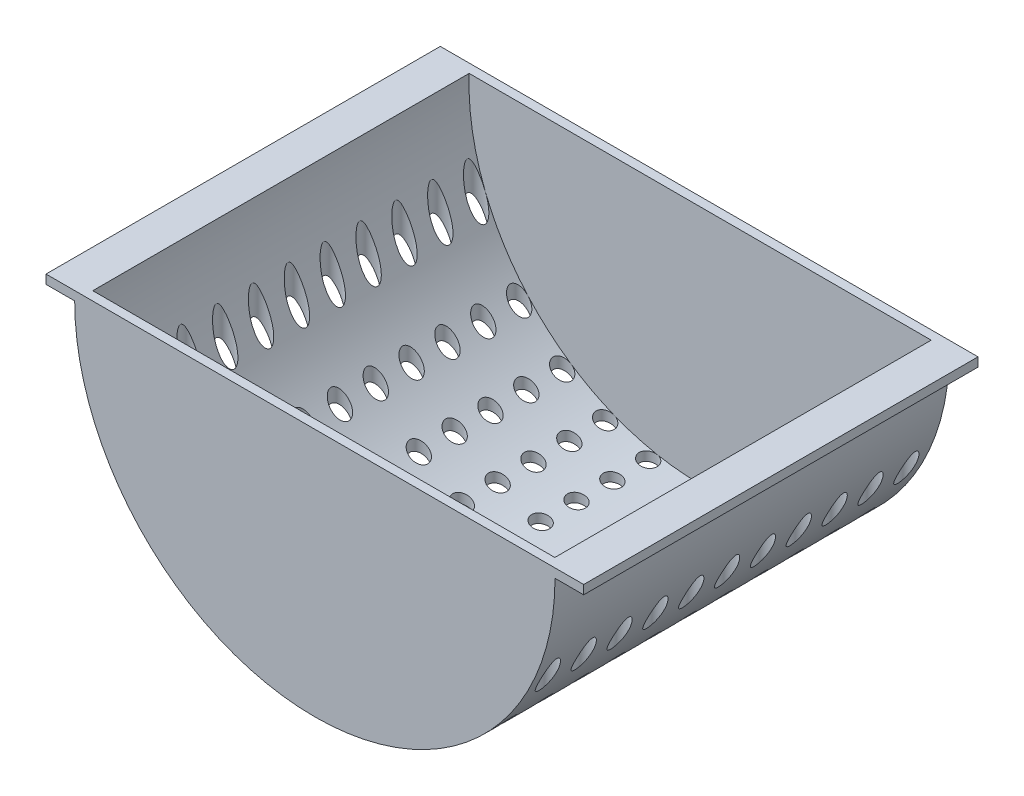
SolidWorks part; units mm, degrees
ref_plane "Plano frontal" through (0, 0, 0) normal (0, 0, 1) x (1, 0, 0)
ref_plane "Plano superior" through (0, 0, 0) normal (0, 1, 0) x (1, 0, 0)
ref_plane "Plano direito" through (0, 0, 0) normal (1, 0, 0) x (0, 0, -1)
sketch "Esboço2" plane through (0, 0, 0) normal (0, 0, 1) x (1, 0, 0)
  line L0 (0, 0) -> (-150, 0)
  line L1 (-150, 0) -> (-150, -2.5)
  line L2 (-150, -2.5) -> (-142, -2.5)
  line L3 (-8, -2.5) -> (0, -2.5)
  line L4 (0, -2.5) -> (0, 0)
  arc A0 (-142, -2.5) -> (-8, -2.5) centre (-75, -2.5) ccw
  dimension "D3" = 8
  dimension "D1" = 150
  dimension "D2" = 2.5
  dimension "D4" = 8
  dimension "D5" = 2.5
extrude "Ressalto-extrusão1" add sketch "Esboço2" along normal blind 110
shell "Casca1" thickness 2.5 removed face at (-75, 0, 55)
sketch "Esboço3" plane through (0, 0, 0) normal (0, 1, 0) x (1, 0, 0)
  line L0 (-75, -107.5) -> (-75, -2.5) construction
  line L3 (-139.4515, -55) -> (-10.5485, -55) construction
  line L4 (-139.4515, -107.5) -> (-139.4515, -2.5) construction
  line L5 (-10.5485, -107.5) -> (-10.5485, -2.5) construction
  circle A0 centre (-75, -55) radius 2.5
  circle A1 centre (-63, -55) radius 2.5
  circle A2 centre (-51, -55) radius 2.5
  circle A3 centre (-39, -55) radius 2.5
  circle A4 centre (-27, -55) radius 2.5
  circle A5 centre (-15, -55) radius 2.5
  circle A6 centre (-63, -45) radius 2.5
  circle A7 centre (-51, -45) radius 2.5
  circle A8 centre (-39, -45) radius 2.5
  circle A9 centre (-27, -45) radius 2.5
  circle A10 centre (-15, -45) radius 2.5
  circle A11 centre (-63, -35) radius 2.5
  circle A12 centre (-51, -35) radius 2.5
  circle A13 centre (-39, -35) radius 2.5
  circle A14 centre (-27, -35) radius 2.5
  circle A15 centre (-15, -35) radius 2.5
  circle A16 centre (-63, -25) radius 2.5
  circle A17 centre (-51, -25) radius 2.5
  circle A18 centre (-39, -25) radius 2.5
  circle A19 centre (-27, -25) radius 2.5
  circle A20 centre (-15, -25) radius 2.5
  circle A21 centre (-63, -15) radius 2.5
  circle A22 centre (-51, -15) radius 2.5
  circle A23 centre (-39, -15) radius 2.5
  circle A24 centre (-27, -15) radius 2.5
  circle A25 centre (-15, -15) radius 2.5
  circle A26 centre (-63, -5) radius 2.5
  circle A27 centre (-51, -5) radius 2.5
  circle A28 centre (-39, -5) radius 2.5
  circle A29 centre (-27, -5) radius 2.5
  circle A30 centre (-15, -5) radius 2.5
  circle A31 centre (-75, -45) radius 2.5
  circle A32 centre (-75, -35) radius 2.5
  circle A33 centre (-75, -25) radius 2.5
  circle A34 centre (-75, -15) radius 2.5
  circle A35 centre (-75, -5) radius 2.5
  circle A36 centre (-75, -105) radius 2.5
  circle A37 centre (-75, -95) radius 2.5
  circle A38 centre (-75, -85) radius 2.5
  circle A39 centre (-75, -75) radius 2.5
  circle A40 centre (-75, -65) radius 2.5
  circle A41 centre (-15, -105) radius 2.5
  circle A42 centre (-27, -105) radius 2.5
  circle A43 centre (-39, -105) radius 2.5
  circle A44 centre (-51, -105) radius 2.5
  circle A45 centre (-63, -105) radius 2.5
  circle A46 centre (-15, -95) radius 2.5
  circle A47 centre (-27, -95) radius 2.5
  circle A48 centre (-39, -95) radius 2.5
  circle A49 centre (-51, -95) radius 2.5
  circle A50 centre (-63, -95) radius 2.5
  circle A51 centre (-15, -85) radius 2.5
  circle A52 centre (-27, -85) radius 2.5
  circle A53 centre (-39, -85) radius 2.5
  circle A54 centre (-51, -85) radius 2.5
  circle A55 centre (-63, -85) radius 2.5
  circle A56 centre (-15, -75) radius 2.5
  circle A57 centre (-27, -75) radius 2.5
  circle A58 centre (-39, -75) radius 2.5
  circle A59 centre (-51, -75) radius 2.5
  circle A60 centre (-63, -75) radius 2.5
  circle A61 centre (-15, -65) radius 2.5
  circle A62 centre (-27, -65) radius 2.5
  circle A63 centre (-39, -65) radius 2.5
  circle A64 centre (-51, -65) radius 2.5
  circle A65 centre (-63, -65) radius 2.5
  circle A66 centre (-87, -65) radius 2.5
  circle A67 centre (-99, -65) radius 2.5
  circle A68 centre (-111, -65) radius 2.5
  circle A69 centre (-123, -65) radius 2.5
  circle A70 centre (-135, -65) radius 2.5
  circle A71 centre (-87, -75) radius 2.5
  circle A72 centre (-99, -75) radius 2.5
  circle A73 centre (-111, -75) radius 2.5
  circle A74 centre (-123, -75) radius 2.5
  circle A75 centre (-135, -75) radius 2.5
  circle A76 centre (-87, -85) radius 2.5
  circle A77 centre (-99, -85) radius 2.5
  circle A78 centre (-111, -85) radius 2.5
  circle A79 centre (-123, -85) radius 2.5
  circle A80 centre (-135, -85) radius 2.5
  circle A81 centre (-87, -95) radius 2.5
  circle A82 centre (-99, -95) radius 2.5
  circle A83 centre (-111, -95) radius 2.5
  circle A84 centre (-123, -95) radius 2.5
  circle A85 centre (-135, -95) radius 2.5
  circle A86 centre (-87, -105) radius 2.5
  circle A87 centre (-99, -105) radius 2.5
  circle A88 centre (-111, -105) radius 2.5
  circle A89 centre (-123, -105) radius 2.5
  circle A90 centre (-135, -105) radius 2.5
  circle A91 centre (-135, -5) radius 2.5
  circle A92 centre (-123, -5) radius 2.5
  circle A93 centre (-111, -5) radius 2.5
  circle A94 centre (-99, -5) radius 2.5
  circle A95 centre (-87, -5) radius 2.5
  circle A96 centre (-135, -15) radius 2.5
  circle A97 centre (-123, -15) radius 2.5
  circle A98 centre (-111, -15) radius 2.5
  circle A99 centre (-99, -15) radius 2.5
  circle A100 centre (-87, -15) radius 2.5
  circle A101 centre (-135, -25) radius 2.5
  circle A102 centre (-123, -25) radius 2.5
  circle A103 centre (-111, -25) radius 2.5
  circle A104 centre (-99, -25) radius 2.5
  circle A105 centre (-87, -25) radius 2.5
  circle A106 centre (-135, -35) radius 2.5
  circle A107 centre (-123, -35) radius 2.5
  circle A108 centre (-111, -35) radius 2.5
  circle A109 centre (-99, -35) radius 2.5
  circle A110 centre (-87, -35) radius 2.5
  circle A111 centre (-135, -45) radius 2.5
  circle A112 centre (-123, -45) radius 2.5
  circle A113 centre (-111, -45) radius 2.5
  circle A114 centre (-99, -45) radius 2.5
  circle A115 centre (-87, -45) radius 2.5
  circle A116 centre (-135, -55) radius 2.5
  circle A117 centre (-123, -55) radius 2.5
  circle A118 centre (-111, -55) radius 2.5
  circle A119 centre (-99, -55) radius 2.5
  circle A120 centre (-87, -55) radius 2.5
  dimension "D1" = 5
extrude "Corte-extrusão1" cut sketch "Esboço3" against normal through all
